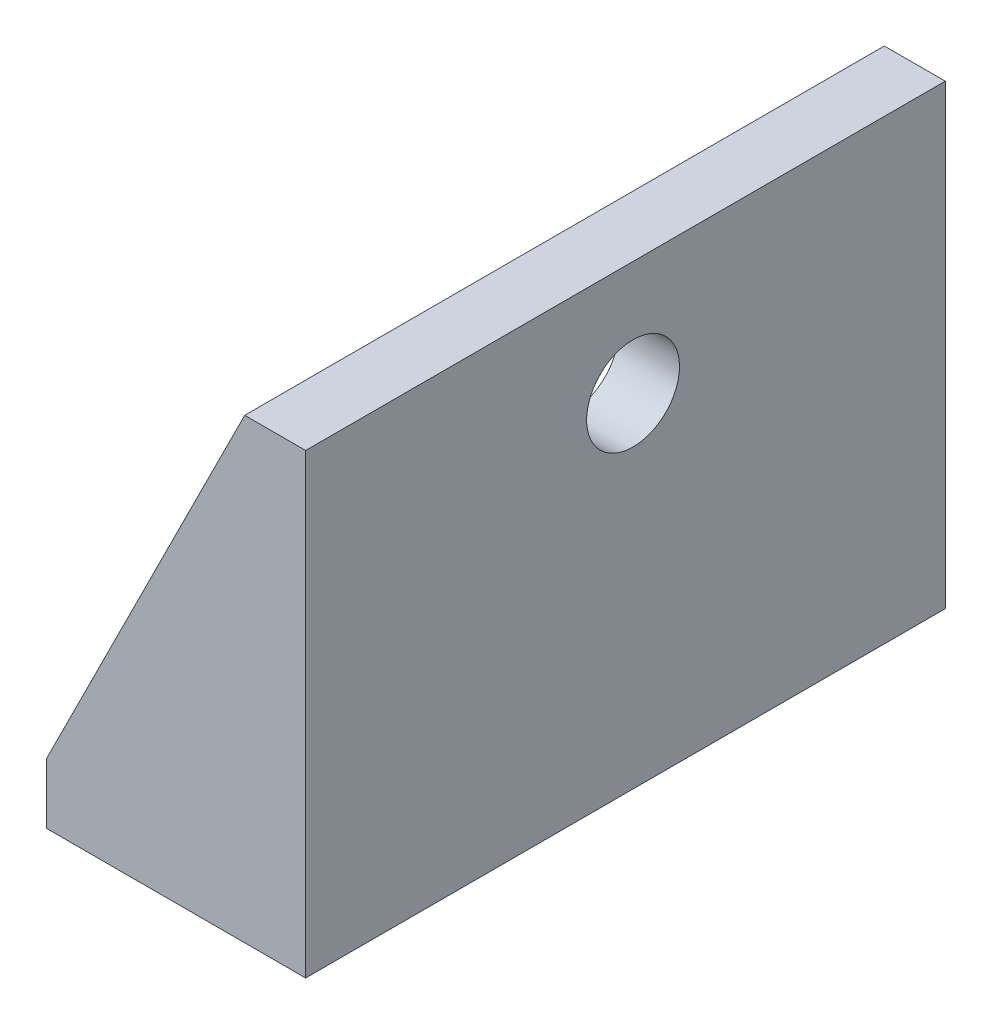
SolidWorks part; units mm, degrees
ref_plane "Front Plane" through (0, 0, 0) normal (0, 0, 1) x (1, 0, 0)
ref_plane "Top Plane" through (0, 0, 0) normal (0, 1, 0) x (1, 0, 0)
ref_plane "Right Plane" through (0, 0, 0) normal (1, 0, 0) x (0, 0, -1)
sketch "Sketch1" plane through (0, 0, 0) normal (0, 1, 0) x (1, 0, 0)
  line L0 (5.5, -21) -> (5.5, 21)
  line L1 (7.5, 21) -> (-7.5, 21)
  line L2 (7.5, 21) -> (7.5, -21)
  line L3 (7.5, -21) -> (-7.5, -21)
  line L4 (-7.5, 21) -> (-7.5, -21)
  line L5 (7.5, 21) -> (-7.5, -21) construction
  line L6 (7.5, -21) -> (-7.5, 21) construction
  circle A0 centre (0.72, 14) radius 1.75
  circle A1 centre (0.72, -14) radius 1.75
  point P0 (0, 0)
  dimension "D4" = 3.5
  dimension "D6" = 3.5
  dimension "D1" = 42
  dimension "D2" = 15
  dimension "D3" = 2
  dimension "D5" = 4.78
  dimension "D7" = 28
  dimension "D8" = 7
extrude "Boss-Extrude1" add sketch "Sketch1" along normal blind 4 contours L1 L4 L3 L0 A1 A0 region at (-1.0628, 0, 0)
extrude "Boss-Extrude2" add sketch "Sketch1<3>" along normal blind 30 contours L3 L2 L1 L0 region at (6.5, 0, 0)
sketch "Sketch1<3>" plane through (0, 0, 0) normal (0, 1, 0) x (1, 0, 0) same geometry as "Sketch1"
sketch "Sketch3" plane through (7.5, 0, 0) normal (1, 0, 0) x (0, 0, -1)
  circle A0 centre (0, 22.5) radius 3.1
  dimension "D1" = 6.2
  dimension "D2" = 22.5
extrude "Cut-Extrude1" cut sketch "Sketch3" against normal blind 50
sketch "Sketch4" plane through (0, 0, 21) normal (0, 0, 1) x (1, 0, 0)
  line L0 (-7.5, 4) -> (5.5, 30)
  line L1 (5.5, 30) -> (5.5, 4) construction
rib "Rib1" sketch "Sketch4" sketch "Sketch4" thickness 2 extrusion direction parallel to sketch draft on no parameters "D1"=2
mirror "Mirror1" about plane through (0, 0, 0) normal (0, 0, 1) of "Rib1"
sketch "Sketch6" plane through (0, 4, 0) normal (0, 1, 0) x (1, 0, 0)
  line L1 (-2.5709, -14) -> (-0.9254, -16.85)
  line L2 (-0.9254, -16.85) -> (2.3654, -16.85)
  line L3 (2.3654, -16.85) -> (4.0109, -14)
  line L4 (4.0109, -14) -> (2.3654, -11.15)
  line L5 (2.3654, -11.15) -> (-0.9254, -11.15)
  line L6 (-0.9254, -11.15) -> (-2.5709, -14)
  line L7 (-2.5709, 14) -> (-0.9254, 11.15)
  line L8 (-0.9254, 11.15) -> (2.3654, 11.15)
  line L9 (2.3654, 11.15) -> (4.0109, 14)
  line L10 (4.0109, 14) -> (2.3654, 16.85)
  line L11 (2.3654, 16.85) -> (-0.9254, 16.85)
  line L12 (-0.9254, 16.85) -> (-2.5709, 14)
  circle A0 centre (0.72, -14) radius 2.85 construction
  circle A1 centre (0.72, 14) radius 2.85 construction
  dimension "D1" = 5.7
  dimension "D2" = 5.7
extrude "Cut-Extrude2" cut sketch "Sketch6" against normal blind 2.5
sketch "Sketch7" plane through (7.5, 0, 0) normal (1, 0, 0) x (0, 0, -1)
  line L0 (21, 0) -> (-21, 0) construction
  line L1 (-21, 0) -> (21, 0)
  line L2 (-21, 0) -> (-21, 30)
  line L3 (-21, 30) -> (21, 30)
  line L4 (21, 0) -> (21, 30)
extrude "Boss-Extrude3" add sketch "Sketch7" along normal blind 2 and the other way blind 2
sketch "Sketch8" plane through (9.5, 0, 0) normal (1, 0, 0) x (0, 0, -1)
  line L0 (21, 0) -> (21, 30) construction
  line L1 (-21, 0) -> (21, 0) construction
  line L2 (-21, 30) -> (-21, 0) construction
  circle A0 centre (0.5, 22.5) radius 3.05
  point P7 (0, 0)
  point P9 (0.1821, 22.3706)
  dimension "D1" = 6.1
  dimension "D2" = 22.5
  dimension "D3" = 20.5
  dimension "D4" = 21.5
extrude "Cut-Extrude3" cut sketch "Sketch8" against normal blind 12
